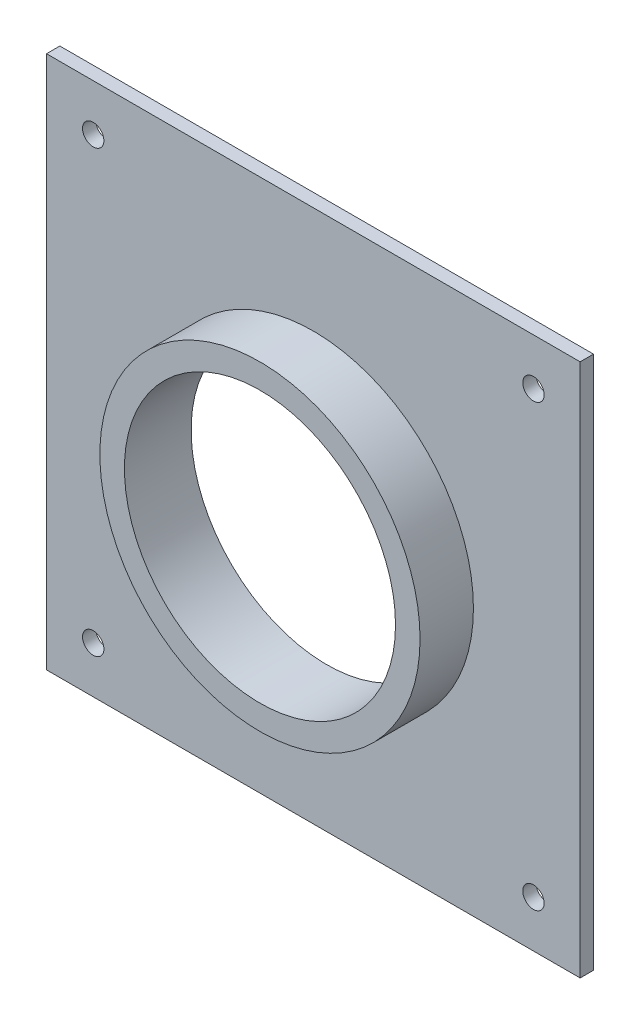
SolidWorks part; units mm, degrees
ref_plane "Front Plane" through (0, 0, 0) normal (1, 0, 0) x (0, 1, 0)
ref_plane "Top Plane" through (0, 0, 0) normal (0, 0, 1) x (0, 1, 0)
ref_plane "Right Plane" through (0, 0, 0) normal (0, 1, 0) x (-1, 0, 0)
sketch "Sketch1" plane through (0, 0, 0) normal (0, 0, 1) x (0, 1, 0)
  line L1 (-20, -20) -> (20, -20)
  line L2 (-20, -20) -> (-20, 20)
  line L3 (-20, 20) -> (20, 20)
  line L4 (20, -20) -> (20, 20)
  line L5 (-20, -20) -> (20, 20) construction
  line L6 (-20, 20) -> (20, -20) construction
  circle A0 centre (0, 0) radius 10.16
  circle A1 centre (0, 0) radius 14
  point P0 (0, 0)
  dimension "D1" = 40
  dimension "D2" = 40
extrude "Boss-Extrude1" add sketch "Sketch1" along normal blind 5 contours A1 A0 region at (0, -13.604, 0)
extrude "Boss-Extrude2" add sketch "Sketch1<3>" along normal blind 1 contours L1 L4 L3 L2 A1 region at (0, -19.4343, 0)
sketch "Sketch1<3>" plane through (0, 0, 0) normal (0, 0, 1) x (0, 1, 0) same geometry as "Sketch1"
sketch "Sketch2" plane through (0, 0, 5) normal (0, 0, 1) x (1, 0, 0)
  circle A0 centre (0, 0) radius 12
  circle A1 centre (0, 0) radius 14
extrude "Cut-Extrude1" cut sketch "Sketch2" against normal up to surface (4 mm away) up to face at (14, 0, 1)
sketch "Sketch3" plane through (0, 0, 1) normal (0, 0, 1) x (1, 0, 0)
  line L0 (20, -20) -> (-20, -20) construction
  line L1 (-20, 20) -> (-19, 20)
  line L2 (-20, 20) -> (-20, -20)
  line L3 (-20, -20) -> (-19, -20)
  line L4 (-19, 20) -> (-19, -20)
  dimension "D1" = 1
extrude "Boss-Extrude3" add sketch "Sketch3" along normal blind 50
sketch "Sketch4" plane through (0, 0, 51) normal (0, 0, 1) x (1, 0, 0)
  line L0 (-19, -20) -> (-19, 20) construction
  line L5 (-19, 4) -> (-17, 5)
  line L6 (-19, -4) -> (-17, -5)
  line L7 (-19, 0) -> (-19, 4)
  line L9 (-17, 5) -> (-17, -5)
  line L11 (-19, 4) -> (-19, -4)
  line L12 (-19, 4) -> (-19, -4)
  point P0 (-19, 0)
  line M10 (-19, -20) -> (-19, 20)
extrude "Boss-Extrude5" add sketch "Sketch4" against normal up to surface (50 mm away) contours L9 L5 L6 M10 region at (-17.963, 0, 51) up to face at (12, 0, 1)
sketch "Sketch5" plane through (-17, 0, 0) normal (1, 0, 0) x (0, 1, 0)
  line L1 (-20, 51) -> (20, 51)
  line L2 (-20, 51) -> (-20, 1)
  line L3 (-20, 1) -> (20, 1)
  line L4 (20, 51) -> (20, 1)
extrude "Cut-Extrude2" cut sketch "Sketch5" against normal blind 22
sketch "Sketch8" plane through (0, 0, 1) normal (0, 0, 1) x (1, 0, 0)
  line L0 (16.5, 20) -> (16.5, 16.5)
  line L1 (-20, 20) -> (-16.5, 20)
  line L2 (-20, 20) -> (-20, 16.5)
  line L3 (-20, 16.5) -> (-16.5, 16.5)
  line L4 (-16.5, 20) -> (-16.5, 16.5)
  line L5 (16.5, 20) -> (20, 20)
  line L6 (20, 20) -> (20, 16.5)
  line L7 (16.5, 16.5) -> (20, 16.5)
  line L8 (16.5, -16.5) -> (16.5, -20)
  line L9 (16.5, -16.5) -> (20, -16.5)
  line L10 (20, -16.5) -> (20, -20)
  line L11 (16.5, -20) -> (20, -20)
  line L12 (-20, -16.5) -> (-20, -20)
  line L13 (-20, -16.5) -> (-16.5, -16.5)
  line L14 (-16.5, -16.5) -> (-16.5, -20)
  line L15 (-20, -20) -> (-16.5, -20)
  point P1 (-16.5, 16.5)
  point P9 (16.5, 16.5)
  point P11 (16.5, -16.5)
  point P18 (-16.5, -16.5)
  dimension "D1" = 3.5
  dimension "D2" = 3.5
  dimension "D3" = 2
  dimension "D4" = 2
hole_wizard "M2 Tapped Hole2" positions "Sketch8" profile "Sketch9" tap size "M2" standard "DIN"
sketch "Sketch9" plane through (-16.5, -16.5, 1) normal (1, 0, 0) x (0, -1, 0)
  line L0 (0, 0) -> (0, 6.4807)
  line L1 (0, 6.4807) -> (0.8, 6)
  line L2 (0.8, 6) -> (0.8, 0)
  line L5 (0.8, 0) -> (0, 0)
  line L10 (0, 6.4807) -> (-0.8, 6) construction
  line L11 (0, -6.35) -> (0, 107.95) construction
  dimension "Tap Drill Dia." = 1.6
  dimension "Tap Drill Depth" = 6
  dimension "Drill Angle" = 118
cosmetic thread "Hole Thread5" parameters "D1"=4, "D2"=2
cosmetic thread "Hole Thread6" parameters "D1"=4, "D2"=2
cosmetic thread "Hole Thread7" parameters "D1"=4, "D2"=2
cosmetic thread "Hole Thread8" parameters "D1"=4, "D2"=2
